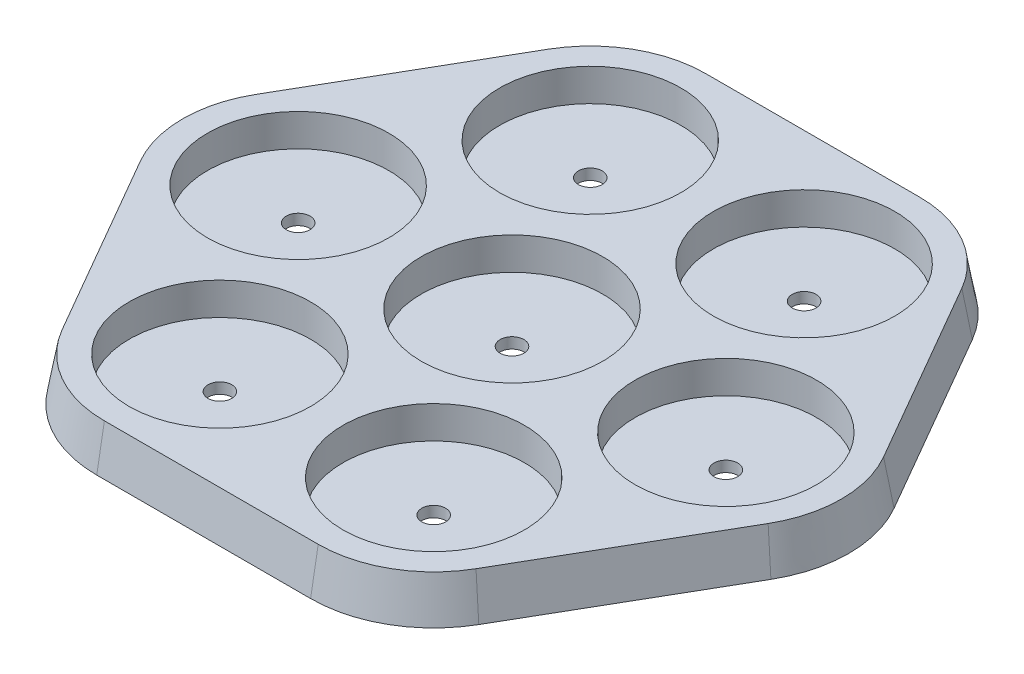
SolidWorks part; units mm, degrees
note: The reader was unsure of these and kept them because the rebuilt part matched: shared geometry of "Sketch1<3>", "Sketch1<4>".
ref_plane "Front Plane" through (0, 0, 0) normal (0, 0, 1) x (1, 0, 0)
ref_plane "Top Plane" through (0, 0, 0) normal (0, 1, 0) x (1, 0, 0)
ref_plane "Right Plane" through (0, 0, 0) normal (1, 0, 0) x (0, 0, -1)
sketch "Sketch1" plane through (0, 0, 0) normal (0, 1, 0) x (1, 0, 0)
  line L0 (0, 0) -> (-9.9, -17.1473) construction
  line L1 (-9.9, -17.1473) -> (-19.8, 0) construction
  line L2 (-19.8, 0) -> (0, 0) construction
  line L3 (9.8727, -5.7) -> (-0.0273, -22.8473)
  line L4 (-9.9, -28.5473) -> (-29.7, -28.5473)
  line L5 (-49.4727, -5.7) -> (-39.5727, -22.8473)
  line L6 (-9.9, -17.1473) -> (-29.7, -17.1473) construction
  line L7 (-29.7, -17.1473) -> (-19.8, 0) construction
  line L9 (0, 0) -> (-9.9, 17.1473) construction
  line L10 (-19.8, 0) -> (-39.6, 0) construction
  line L11 (-39.6, 0) -> (-29.7, -17.1473) construction
  line L12 (-9.9, 17.1473) -> (-19.8, 0) construction
  line L13 (-19.8, 0) -> (-29.7, 17.1473) construction
  line L14 (-29.7, 17.1473) -> (-39.6, 0) construction
  line L15 (-0.0273, 22.8473) -> (9.8727, 5.7)
  line L16 (-9.9, 17.1473) -> (-29.7, 17.1473) construction
  line L17 (-9.9, 28.5473) -> (-29.7, 28.5473)
  line L18 (-39.5727, 22.8473) -> (-49.4727, 5.7)
  circle A0 centre (0, 0) radius 8.4
  circle A1 centre (-19.8, 0) radius 8.4
  circle A2 centre (-9.9, -17.1473) radius 8.4
  circle A3 centre (-9.9, -17.1473) radius 1.1
  circle A4 centre (-19.8, 0) radius 1.1
  circle A5 centre (0, 0) radius 1.1
  circle A6 centre (-9.9, -17.1473) radius 11.4
  circle A7 centre (-19.8, 0) radius 11.4
  circle A8 centre (0, 0) radius 11.4
  circle A9 centre (-29.7, -17.1473) radius 1.1
  circle A10 centre (-29.7, -17.1473) radius 8.4
  circle A11 centre (-29.7, -17.1473) radius 11.4
  circle A12 centre (-39.6, 0) radius 1.1
  circle A13 centre (-39.6, 0) radius 8.4
  circle A14 centre (-39.6, 0) radius 11.4
  circle A15 centre (-9.9, 17.1473) radius 1.1
  circle A16 centre (-9.9, 17.1473) radius 8.4
  circle A17 centre (-9.9, 17.1473) radius 11.4
  circle A18 centre (-29.7, 17.1473) radius 1.1
  circle A19 centre (-29.7, 17.1473) radius 8.4
  circle A20 centre (-29.7, 17.1473) radius 11.4
  dimension "D1" = 16.8
  dimension "D4" = 16.8
  dimension "D5" = 16.8
  dimension "D7" = 2.2
  dimension "D8" = 2.2
  dimension "D9" = 2.2
  dimension "D10" = 22.8
  dimension "D11" = 22.8
  dimension "D12" = 22.8
  dimension "D14" = 2.2
  dimension "D15" = 16.8
  dimension "D16" = 22.8
  dimension "D18" = 16.8
  dimension "D19" = 22.8
  dimension "D20" = 2.2
  dimension "D22" = 2.2
  dimension "D23" = 22.8
  dimension "D24" = 16.8
  dimension "D29" = 2.2
  dimension "D30" = 22.8
  dimension "D31" = 16.8
  dimension "D2" = 60
  dimension "D3" = 60
  dimension "D6" = 19.8
  dimension "D13" = 60
  dimension "D17" = 60
  dimension "D21" = 60
  dimension "D25" = 60
  dimension "D26" = 60
  dimension "D27" = 60
  dimension "D28" = 60
extrude "Boss-Extrude1" add sketch "Sketch1" along normal blind 4 draft 10
extrude "Cut-Extrude1" cut sketch "Sketch1<3>" against normal blind 4 from surface at 4 contours A3 | A5 | A9 | A12 | A15 | A18 | A4 starting at face at (-19.8, 4, 0)
sketch "Sketch1<3>" plane through (0, 0, 0) normal (0, 1, 0) x (1, 0, 0) same geometry as "Sketch1"
extrude "Cut-Extrude2" cut sketch "Sketch1<4>" against normal blind 3 from surface at 4 contours A1 A4 | A2 A3 | A0 A5 | A10 A9 | A13 A12 | A16 A15 | A19 A18 starting at face at (-9.9, 4, -16.0473)
sketch "Sketch1<4>" plane through (0, 0, 0) normal (0, 1, 0) x (1, 0, 0) same geometry as "Sketch1"
